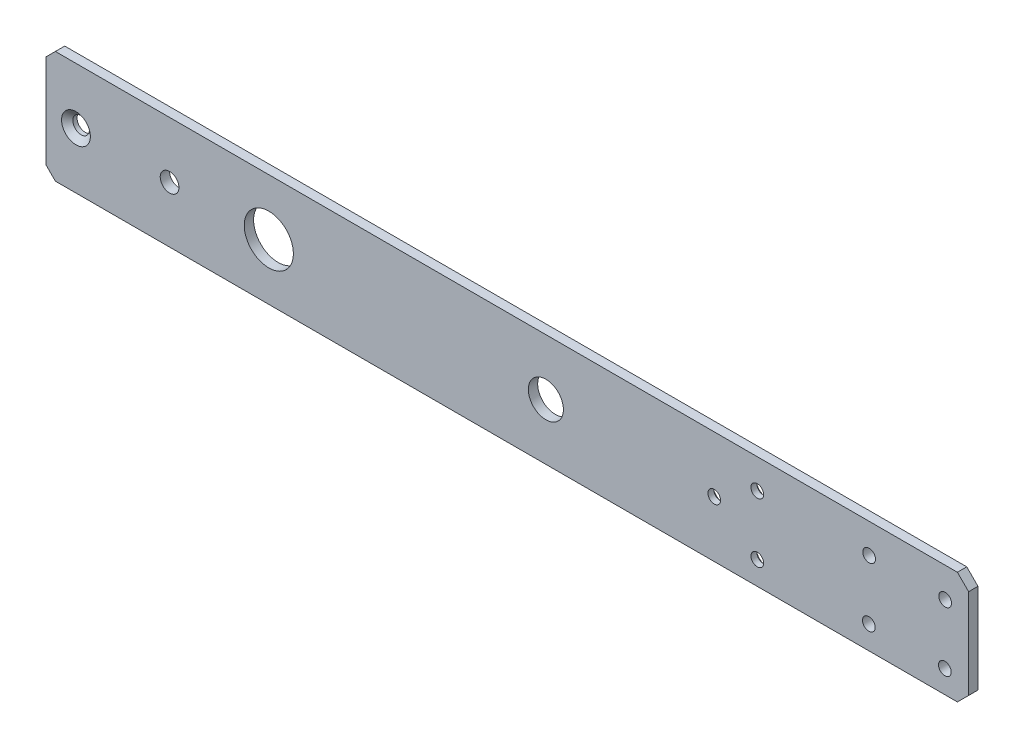
SolidWorks part; units mm, degrees
material "6061-T6 (SS)"
ref_plane "Front Plane" through (0, 0, 0) normal (0, 0, 1) x (1, 0, 0)
ref_plane "Top Plane" through (0, 0, 0) normal (0, 1, 0) x (1, 0, 0)
ref_plane "Right Plane" through (0, 0, 0) normal (1, 0, 0) x (0, 0, -1)
sketch "Sketch1" plane through (0, 0, 0) normal (0, 0, 1) x (1, 0, 0)
  line L0 (0, 19.05) -> (-28.575, 19.05)
  line L1 (0, -19.05) -> (247.2819, -19.05)
  line L2 (0, -19.05) -> (0, 19.05) construction
  line L3 (0, 19.05) -> (254, 19.05)
  line L5 (-28.575, 19.05) -> (-28.575, -19.05)
  line L6 (-28.575, -19.05) -> (0, -19.05)
  line L8 (254, 19.05) -> (247.2819, -19.05)
  circle A1 centre (0, 0) radius 8.3344
  dimension "D3" = 16.6687
  dimension "D1" = 38.1
  dimension "D2" = 254
  dimension "D4" = 80
extrude "Boss-Extrude1" add sketch "Sketch1" along normal mid plane 3.175
hole_wizard "#6 Clearance Hole3" positions "Sketch8" profile "Sketch7" hole size "#6" standard "ANSI Inch" end condition through all
sketch "Sketch8" plane through (0, 0, 1.5875) normal (0, 0, 1) x (1, 0, 0)
  line L9 (159.3222, 8.9914) -> (175.5726, 8.9914) construction
  line L12 (159.3222, -11.1439) -> (172.0222, -11.1439) construction
  line L13 (159.3222, 19.05) -> (159.3222, -19.05) construction
  line L26 (254, 19.05) -> (-28.575, 19.05) construction
  line L28 (-28.575, -19.05) -> (247.2819, -19.05) construction
  line L29 (159.3222, 0) -> (151.0672, 0) construction
  line L30 (165.6722, 8.9914) -> (165.6722, -11.1439) construction
  line L31 (170.6012, -19.2024) -> (177.3462, 19.05) construction
  point P0 (229.3887, 8.9238)
  point P3 (229.2824, -11.3468)
  point P6 (203.5032, -11.1439)
  point P9 (203.6088, 8.9914)
  point P12 (165.6722, 8.9914)
  point P15 (165.6722, -11.1439)
  point P18 (151.0672, 0)
  dimension "D1" = 6.35
  dimension "D2" = 8.255
sketch "Sketch7" plane through (229.3887, 8.9238, 1.5875) normal (1, 0, 0) x (0, -1, 0)
  line L0 (0, 0) -> (0, 3.175)
  line L1 (0, 3.175) -> (2.1526, 3.175)
  line L2 (2.1526, 3.175) -> (2.1526, 0)
  line L5 (2.1526, 0) -> (0, 0)
  line L11 (0, -6.35) -> (0, 107.95) construction
  dimension "Thru Hole Dia." = 4.3053
  dimension "Thru Hole Depth" = 3.175
sketch "Sketch9" plane through (0, 0, 1.5875) normal (0, 0, 1) x (1, 0, 0)
  line L0 (254, 19.05) -> (247.2819, -19.05)
  line L1 (254, 19.05) -> (237.3521, 19.05)
  line L2 (254, 19.05) -> (-28.575, 19.05) construction
  line L3 (237.3521, 19.05) -> (237.3521, -19.05)
  line L4 (-28.575, -19.05) -> (247.2819, -19.05) construction
  line L5 (237.3521, -19.05) -> (247.2819, -19.05)
  line L6 (243.8073, 17.5595) -> (237.0893, -20.5405) construction
extrude "Cut-Extrude1" cut sketch "Sketch9" against normal through all
chamfer "Chamfer1" distance 3.81 angle 45 4 edges at (-28.575, -19.05, 0) (-28.575, 19.05, 0) (237.3521, 19.05, 0) (237.3521, -19.05, 0)
sketch "Sketch10" plane through (0, 0, 1.5875) normal (0, 0, 1) x (1, 0, 0)
  line L0 (-24.765, -19.05) -> (233.5421, -19.05) construction
  line L1 (-24.765, -19.05) -> (-75.565, -19.05)
  line L2 (-24.765, -19.05) -> (-24.765, 19.05)
  line L3 (-24.765, 19.05) -> (-75.565, 19.05)
  line L4 (-75.565, -19.05) -> (-75.565, 19.05)
  dimension "D1" = 50.8
extrude "Boss-Extrude2" add sketch "Sketch10" against normal through all
chamfer "Chamfer2" distance 3.175 angle 45 2 edges at (-75.565, -19.05, 0) (-75.565, 19.05, 0)
hole_wizard "CSK for #10 Flat Head Machine Screw (100)1" positions "Sketch11" profile "Sketch12" countersink size "#10" standard "ANSI Inch" end condition through all
sketch "Sketch11" plane through (0, 0, 1.5875) normal (0, 0, 1) x (1, 0, 0)
  line L0 (0, 0) -> (-75.565, 0) construction
  line L1 (-75.565, 15.875) -> (-75.565, -15.875) construction
  point P0 (-65.405, 0)
  dimension "D1" = 10.16
sketch "Sketch12" plane through (-65.405, 0, 1.5875) normal (1, 0, 0) x (0, -1, 0)
  line L0 (0, 0) -> (0, 3.175)
  line L1 (0, 3.175) -> (2.8067, 3.175)
  line L2 (2.8067, 3.175) -> (2.8067, 1.7477)
  line L3 (2.8067, 1.7477) -> (4.8895, 0)
  line L5 (4.8895, 0) -> (0, 0)
  line L6 (-2.8067, 1.7477) -> (-4.8895, 0) construction
  line L11 (0, -6.35) -> (0, 107.95) construction
  dimension "Thru Hole Dia." = 5.6134
  dimension "Thru Hole Depth" = 3.175
  dimension "Near C'Sink Dia." = 9.779
  dimension "Near C'Sink Angle" = 100
hole_wizard "1/4 (0.25) Diameter Hole1" positions "Sketch13" profile "Sketch14" hole size "1/4" standard "ANSI Inch" end condition through all
sketch "Sketch13" plane through (0, 0, 1.5875) normal (0, 0, 1) x (1, 0, 0)
  line L0 (-75.565, 0) -> (-33.655, 0) construction
  line L1 (-75.565, 15.875) -> (-75.565, -15.875) construction
  circle A0 centre (-65.405, 0) radius 4.8895 construction
  point P0 (-33.655, 0)
  dimension "D1" = 31.75
sketch "Sketch14" plane through (-33.655, 0, 1.5875) normal (1, 0, 0) x (0, -1, 0)
  line L0 (0, 0) -> (0, 3.175)
  line L1 (0, 3.175) -> (3.175, 3.175)
  line L2 (3.175, 3.175) -> (3.175, 0)
  line L5 (3.175, 0) -> (0, 0)
  line L11 (0, -6.35) -> (0, 107.95) construction
  dimension "Thru Hole Dia." = 6.35
  dimension "Thru Hole Depth" = 3.175
hole_wizard "CSK for #6 Flat Head Machine Screw (100)1" positions "Sketch15" profile "Sketch16" countersink size "#6" standard "ANSI Inch" end condition through all
sketch "Sketch15" plane through (0, 0, -1.5875) normal (0, 0, -1) x (-1, 0, 0)
  point P0 (-151.0672, 0)
  point P3 (-165.6722, -11.1439)
  point P6 (-165.6722, 8.9914)
sketch "Sketch16" plane through (151.0672, 0, -1.5875) normal (1, 0, 0) x (0, 1, 0)
  line L0 (0, 0) -> (0, 3.175)
  line L1 (0, 3.175) -> (2.1526, 3.175)
  line L2 (2.1526, 3.175) -> (2.1526, 1.1669)
  line L3 (2.1526, 1.1669) -> (3.5433, 0)
  line L5 (3.5433, 0) -> (0, 0)
  line L6 (-2.1526, 1.1669) -> (-3.5433, 0) construction
  line L11 (0, -6.35) -> (0, 107.95) construction
  dimension "Thru Hole Dia." = 4.3053
  dimension "Thru Hole Depth" = 3.175
  dimension "Near C'Sink Dia." = 7.0866
  dimension "Near C'Sink Angle" = 100
hole_wizard "15/32 (0.46875) Diameter Hole1" positions "Sketch17" profile "Sketch18" hole size "15/32" standard "ANSI Inch" end condition through all
sketch "Sketch17" plane through (0, 0, -1.5875) normal (0, 0, -1) x (-1, 0, 0)
  line L0 (75.565, 15.875) -> (75.565, -15.875) construction
  point P0 (-93.9672, 0)
  dimension "D1" = 169.5322
sketch "Sketch18" plane through (93.9672, 0, -1.5875) normal (1, 0, 0) x (0, 1, 0)
  line L0 (0, 0) -> (0, 3.175)
  line L1 (0, 3.175) -> (5.9531, 3.175)
  line L2 (5.9531, 3.175) -> (5.9531, 0)
  line L5 (5.9531, 0) -> (0, 0)
  line L11 (0, -6.35) -> (0, 107.95) construction
  dimension "Thru Hole Dia." = 11.9062
  dimension "Thru Hole Depth" = 3.175
